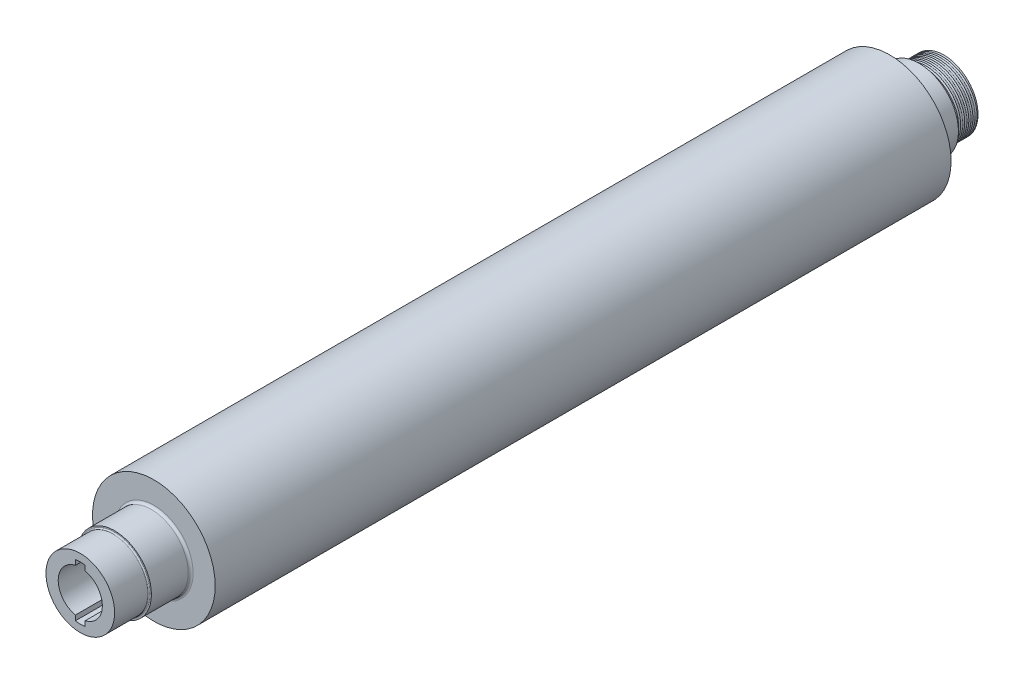
SolidWorks part; units mm, degrees
ref_plane "Front Plane" through (0, 0, 0) normal (0, 0, 1) x (1, 0, 0)
ref_plane "Top Plane" through (0, 0, 0) normal (0, 1, 0) x (1, 0, 0)
ref_plane "Right Plane" through (0, 0, 0) normal (1, 0, 0) x (0, 0, -1)
sketch "Sketch1" plane through (0, 0, 0) normal (0, 0, 1) x (1, 0, 0)
  line L0 (-12.5, 0) -> (12.5, 0) construction
  line L1 (0, 12.5) -> (0, -12.5) construction
  circle A0 centre (0, 0) radius 12.5
  dimension "D3" = 25
  dimension "D1" = 25
  dimension "D2" = 25
extrude "Boss-Extrude1" add sketch "Sketch1" along normal blind 150
sketch "Sketch2" plane through (0, 0, 150) normal (0, 0, 1) x (1, 0, 0)
  circle A0 centre (0, 0) radius 7.5
  dimension "D1" = 15
extrude "Boss-Extrude2" add sketch "Sketch2" along normal blind 8
fillet "Fillet1" radius 0.5 1 edges at (7.5, 0, 150)
sketch "Sketch3" plane through (0, 0, 158) normal (0, 0, 1) x (1, 0, 0)
  circle A0 centre (0, 0) radius 7
  dimension "D1" = 14
extrude "Boss-Extrude3" add sketch "Sketch3" along normal blind 7
fillet "Fillet2" radius 0.25 1 edges at (7, 0, 158)
sketch "Sketch5" plane through (0, 0, 165) normal (0, 0, 1) x (1, 0, 0)
  circle A0 centre (0, 0) radius 4.5
  dimension "D1" = 9
extrude "Cut-Extrude1" cut sketch "Sketch5" against normal through all
sketch "Sketch6" plane through (0, 0, 165) normal (0, 0, 1) x (1, 0, 0)
  circle A0 centre (0, 0) radius 5.5
  dimension "D1" = 11
extrude "Cut-Extrude2" cut sketch "Sketch6" against normal blind 15
ref_plane "Plane1" through (0, 0, 158) normal (0, 0, 1) x (1, 0, 0)
sketch "Sketch13" plane through (0, 0, 158) normal (0, 0, 1) x (1, 0, 0)
  circle A0 centre (0, 0) radius 4.5
  dimension "D1" = 9
sketch "Sketch7" plane through (0, 0, 165) normal (0, 0, 1) x (1, 0, 0)
  line L0 (-4.5, 0) -> (4.5, 0)
  line L2 (-1, 5.4083) -> (-1, -5.4083)
  line L4 (1, 5.4083) -> (1, -5.4083)
  arc A0 (1, -5.4083) -> (1, 5.4083) centre (0, 0) ccw
  circle A1 centre (0, 0) radius 4.5 construction
  arc A2 (-1, 5.4083) -> (-1, -5.4083) centre (0, 0) ccw
  arc A3 (-1, 4.3875) -> (-1, -4.3875) centre (0, 0) ccw
  arc A4 (1, -4.3875) -> (1, 4.3875) centre (0, 0) ccw
  circle M1 centre (0, 0) radius 5.5
  dimension "D1" = 11
  dimension "D4" = 9
  dimension "D2" = 2
  dimension "D3" = 3.5
extrude "Boss-Extrude4" add sketch "Sketch7" against normal blind 15 contours A3 L2 M1 | A4 L4 M1
sketch "Sketch8" plane through (0, 0, 0) normal (0, 0, -1) x (-1, 0, 0)
  circle A0 centre (0, 0) radius 8 construction
  circle A1 centre (0, 0) radius 12.5
  circle A2 centre (0, 0) radius 12.5
  circle A3 centre (0, 0) radius 8
  circle M2 centre (0, 0) radius 4.5
  dimension "D1" = 0
extrude "Boss-Extrude5" add sketch "Sketch8" along normal blind 6 contours A3 M2
fillet "Fillet3" radius 0.5 1 edges at (8, 0, 0)
sketch "Sketch9" plane through (0, 0, -6) normal (0, 0, -1) x (-1, 0, 0)
  circle A0 centre (0, 0) radius 6.5
  circle A1 centre (0, 0) radius 4.5 construction
  circle A2 centre (0, 0) radius 4.5
  dimension "D1" = 13
extrude "Boss-Extrude6" add sketch "Sketch9" along normal blind 1
sketch "Sketch10" plane through (0, 0, -7) normal (0, 0, -1) x (-1, 0, 0)
  circle A0 centre (0, 0) radius 7
  circle A1 centre (0, 0) radius 4.5 construction
  circle A2 centre (0, 0) radius 4.5
  dimension "D1" = 14
extrude "Boss-Extrude7" add sketch "Sketch10" along normal blind 4
sketch "Sketch11" plane through (0, 0, -11) normal (0, 0, -1) x (-1, 0, 0)
  circle A0 centre (0, 0) radius 7
  dimension "D1" = 14
curve "Helix/Spiral1" pitch 0.8333 height 4.7917 turns 5.75
sketch "Sketch12" plane through (0, 0, 0) normal (1, 0, 0) x (0, 0, -1)
  circle A0 centre (6.2083, 7) radius 0.2
  dimension "D1" = 0.4
sweep "Cut-Sweep1" cut profiles "Sketch12" path "Helix/Spiral1"
